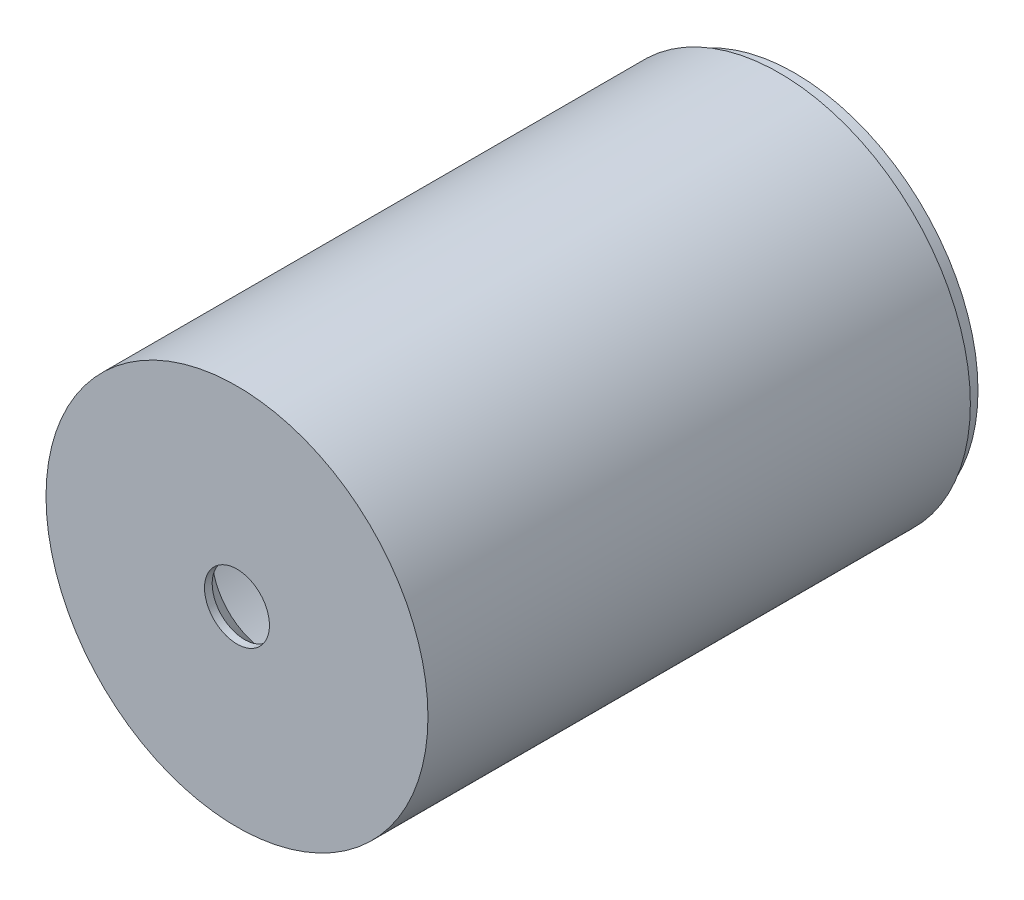
SolidWorks part; units mm, degrees
ref_plane "정면" through (0, 0, 0) normal (0, 0, 1) x (1, 0, 0)
ref_plane "윗면" through (0, 0, 0) normal (0, 1, 0) x (1, 0, 0)
ref_plane "우측면" through (0, 0, 0) normal (1, 0, 0) x (0, 0, -1)
sketch "스케치1" plane through (0, 0, 0) normal (0, 0, 1) x (1, 0, 0)
  circle A0 centre (0, 0) radius 2.3
  circle A1 centre (0, 0) radius 2.5
  dimension "D1" = 5
  dimension "D2" = 4.6
extrude "보스-돌출1" add sketch "스케치1" along normal blind 6.3
sketch "스케치2" plane through (0, 0, 6.3) normal (0, 0, 1) x (1, 0, 0)
  circle A0 centre (0, 0) radius 2.5 construction
  circle A1 centre (0, 0) radius 2.5
extrude "보스-돌출2" add sketch "스케치2" along normal blind 1
sketch "스케치4" plane through (0, 0, 6.3) normal (0, 0, -1) x (-1, 0, 0)
  circle A0 centre (0, 0) radius 0.425
  dimension "D1" = 0.85
extrude "컷-돌출1" cut sketch "스케치4" against normal through all
sketch "스케치5" plane through (0, 0, 6.3) normal (0, 0, -1) x (-1, 0, 0)
  circle A0 centre (0, 0) radius 1.675
  dimension "D1" = 3.35
extrude "컷-돌출2" cut sketch "스케치5" against normal blind 0.6
sketch "스케치6" plane through (0, 0, 6.3) normal (0, 0, -1) x (-1, 0, 0)
  circle A0 centre (0, 0) radius 2.2
  dimension "D1" = 4.4
extrude "컷-돌출3" cut sketch "스케치6" against normal blind 0.5
fillet "필렛1" radius 0.1 1 edges at (-2.2, 0, 6.3)
fillet "필렛2" radius 0.1 1 edges at (-1.675, 0, 6.8)
chamfer "모따기2" distance 0.3 1 edges at (-0.425, 0, 6.9)
sketch "스케치9" plane through (0, 0, 0) normal (0, 0, -1) x (-1, 0, 0)
  circle A2 centre (0, 0) radius 2.4
  circle A4 centre (0, 0) radius 2.5 construction
  circle A5 centre (0, 0) radius 2.5
  dimension "D1" = 4.8
extrude "컷-돌출4" cut sketch "스케치9" against normal blind 0.2
